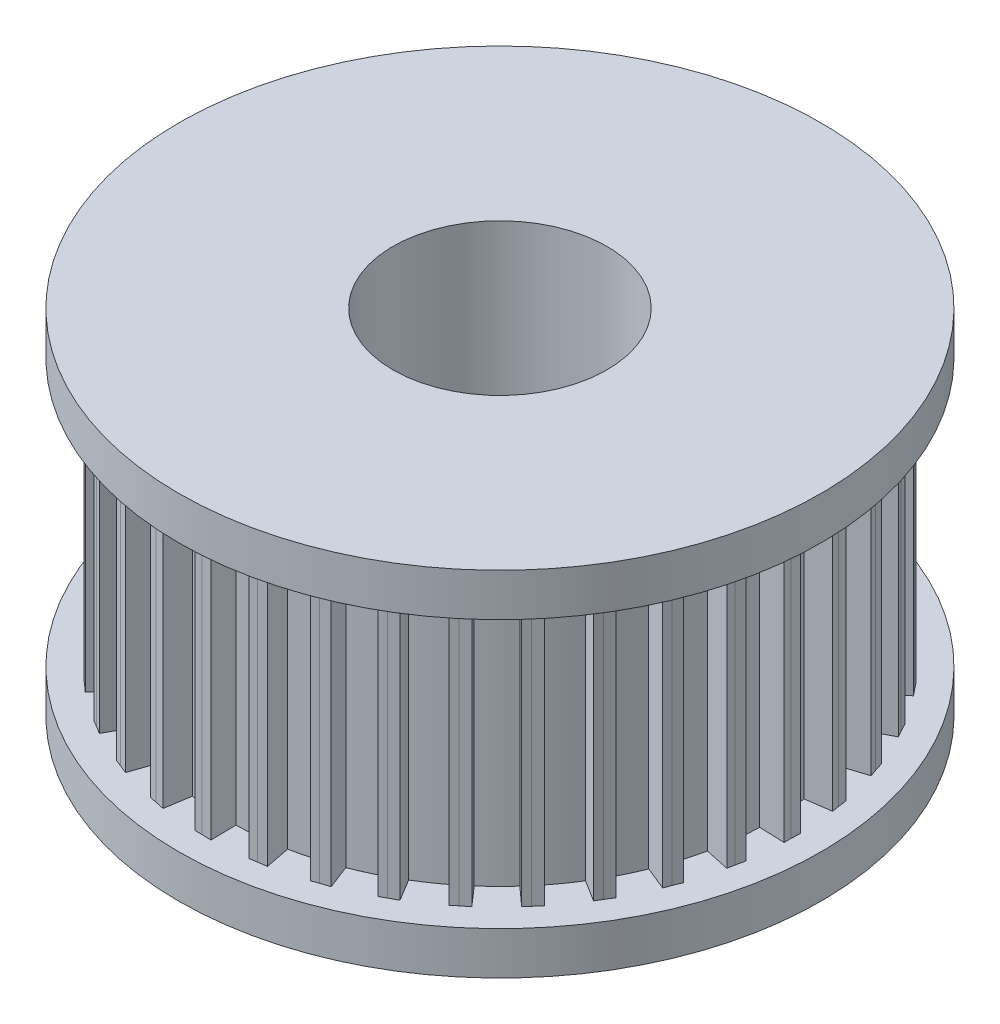
SolidWorks part; units mm, degrees
ref_plane "Front Plane" through (0, 0, 0) normal (0, 0, 1) x (1, 0, 0)
ref_plane "Top Plane" through (0, 0, 0) normal (0, 1, 0) x (1, 0, 0)
ref_plane "Right Plane" through (0, 0, 0) normal (1, 0, 0) x (0, 0, -1)
sketch "Sketch1" plane through (0, 0, 0) normal (0, 1, 0) x (1, 0, 0)
  circle A0 centre (0, 0) radius 6.35
  circle A1 centre (0, 0) radius 19.05
  dimension "D1" = 12.7
  dimension "D2" = 38.1
extrude "Boss-Extrude1" add sketch "Sketch1" along normal blind 2.54
sketch "Sketch2" plane through (0, 2.54, 0) normal (0, 1, 0) x (1, 0, 0)
  line L0 (-6.3084, 16.3202) -> (-5.7627, 14.9085)
  line L1 (-8.5703, 15.2299) -> (-8.2044, 15.4358)
  line L2 (-8.2044, 15.4358) -> (-7.5017, 14.1137)
  line L3 (-7.5017, 14.1137) -> (-8.2044, 15.4358)
  line L4 (-8.5703, 15.2299) -> (-9.0465, 14.9768)
  line L5 (-9.0465, 14.9768) -> (-8.264, 13.6813)
  line L6 (-5.7955, 16.4867) -> (-6.3084, 16.3202)
  line L7 (-5.7955, 16.4867) -> (-5.3994, 16.626)
  line L8 (-5.3994, 16.626) -> (-4.9369, 15.2019)
  line L9 (-3.3786, 17.1677) -> (-3.0864, 15.6827)
  line L10 (-2.8446, 17.2426) -> (-3.3786, 17.1677)
  line L11 (-2.8446, 17.2426) -> (-2.4303, 17.311)
  line L12 (-2.4303, 17.311) -> (-2.2221, 15.8283)
  line L13 (-0.3461, 17.4935) -> (-0.3162, 15.9804)
  line L14 (0.1928, 17.4746) -> (-0.3461, 17.4935)
  line L15 (0.1928, 17.4746) -> (0.6126, 17.47)
  line L16 (0.6126, 17.47) -> (0.5602, 15.9737)
  line L17 (2.6968, 17.2879) -> (2.4636, 15.7925)
  line L18 (3.2243, 17.1757) -> (2.6968, 17.2879)
  line L19 (3.2243, 17.1757) -> (3.637, 17.0982)
  line L20 (3.637, 17.0982) -> (3.3255, 15.6337)
  line L21 (5.6579, 16.5569) -> (5.1685, 15.1248)
  line L22 (6.1579, 16.3548) -> (5.6579, 16.5569)
  line L23 (6.1579, 16.3548) -> (6.5508, 16.2069)
  line L24 (6.5508, 16.2069) -> (5.9897, 14.8188)
  line L25 (8.447, 15.3229) -> (7.7163, 13.9975)
  line L26 (8.9043, 15.0371) -> (8.447, 15.3229)
  line L27 (8.9043, 15.0371) -> (9.2656, 14.8231)
  line L28 (9.2656, 14.8231) -> (8.472, 13.5535)
  line L29 (10.9795, 13.6233) -> (10.0298, 12.4449)
  line L30 (11.3802, 13.2624) -> (10.9795, 13.6233)
  line L31 (11.3802, 13.2624) -> (11.6988, 12.989)
  line L32 (11.6988, 12.989) -> (10.6968, 11.8765)
  line L33 (13.1783, 11.5098) -> (12.0384, 10.5142)
  line L34 (13.5103, 11.0848) -> (13.1783, 11.5098)
  line L35 (13.5103, 11.0848) -> (13.7766, 10.7602)
  line L36 (13.7766, 10.7602) -> (12.5966, 9.8386)
  line L37 (14.9768, 9.0465) -> (13.6813, 8.264)
  line L38 (15.2299, 8.5703) -> (14.9768, 9.0465)
  line L39 (15.2299, 8.5703) -> (15.4358, 8.2044)
  line L40 (15.4358, 8.2044) -> (14.1137, 7.5017)
  line L41 (16.3202, 6.3084) -> (14.9085, 5.7627)
  line L42 (16.4867, 5.7955) -> (16.3202, 6.3084)
  line L43 (16.4867, 5.7955) -> (16.626, 5.3994)
  line L44 (16.626, 5.3994) -> (15.2019, 4.9369)
  line L45 (17.1677, 3.3786) -> (15.6827, 3.0864)
  line L46 (17.2426, 2.8446) -> (17.1677, 3.3786)
  line L47 (17.2426, 2.8446) -> (17.311, 2.4303)
  line L48 (17.311, 2.4303) -> (15.8283, 2.2221)
  line L49 (17.4935, 0.3461) -> (15.9804, 0.3162)
  line L50 (17.4746, -0.1928) -> (17.4935, 0.3461)
  line L51 (17.4746, -0.1928) -> (17.47, -0.6126)
  line L52 (17.47, -0.6126) -> (15.9737, -0.5602)
  line L53 (17.2879, -2.6968) -> (15.7925, -2.4636)
  line L54 (17.1757, -3.2243) -> (17.2879, -2.6968)
  line L55 (17.1757, -3.2243) -> (17.0982, -3.637)
  line L56 (17.0982, -3.637) -> (15.6337, -3.3255)
  line L57 (16.5569, -5.6579) -> (15.1248, -5.1685)
  line L58 (16.3548, -6.1579) -> (16.5569, -5.6579)
  line L59 (16.3548, -6.1579) -> (16.2069, -6.5508)
  line L60 (16.2069, -6.5508) -> (14.8188, -5.9897)
  line L61 (15.3229, -8.447) -> (13.9975, -7.7163)
  line L62 (15.0371, -8.9043) -> (15.3229, -8.447)
  line L63 (15.0371, -8.9043) -> (14.8231, -9.2656)
  line L64 (14.8231, -9.2656) -> (13.5535, -8.472)
  line L65 (13.6233, -10.9795) -> (12.4449, -10.0298)
  line L66 (13.2624, -11.3802) -> (13.6233, -10.9795)
  line L67 (13.2624, -11.3802) -> (12.989, -11.6988)
  line L68 (12.989, -11.6988) -> (11.8765, -10.6968)
  line L69 (11.5098, -13.1783) -> (10.5142, -12.0384)
  line L70 (11.0848, -13.5103) -> (11.5098, -13.1783)
  line L71 (11.0848, -13.5103) -> (10.7602, -13.7766)
  line L72 (10.7602, -13.7766) -> (9.8386, -12.5966)
  line L73 (9.0465, -14.9768) -> (8.264, -13.6813)
  line L74 (8.5703, -15.2299) -> (9.0465, -14.9768)
  line L75 (8.5703, -15.2299) -> (8.2044, -15.4358)
  line L76 (8.2044, -15.4358) -> (7.5017, -14.1137)
  line L77 (6.3084, -16.3202) -> (5.7627, -14.9085)
  line L78 (5.7955, -16.4867) -> (6.3084, -16.3202)
  line L79 (5.7955, -16.4867) -> (5.3994, -16.626)
  line L80 (5.3994, -16.626) -> (4.9369, -15.2019)
  line L81 (3.3786, -17.1677) -> (3.0864, -15.6827)
  line L82 (2.8446, -17.2426) -> (3.3786, -17.1677)
  line L83 (2.8446, -17.2426) -> (2.4303, -17.311)
  line L84 (2.4303, -17.311) -> (2.2221, -15.8283)
  line L85 (0.3461, -17.4935) -> (0.3162, -15.9804)
  line L86 (-0.1928, -17.4746) -> (0.3461, -17.4935)
  line L87 (-0.1928, -17.4746) -> (-0.6126, -17.47)
  line L88 (-0.6126, -17.47) -> (-0.5602, -15.9737)
  line L89 (-2.6968, -17.2879) -> (-2.4636, -15.7925)
  line L90 (-3.2243, -17.1757) -> (-2.6968, -17.2879)
  line L91 (-3.2243, -17.1757) -> (-3.637, -17.0982)
  line L92 (-3.637, -17.0982) -> (-3.3255, -15.6337)
  line L93 (-5.6579, -16.5569) -> (-5.1685, -15.1248)
  line L94 (-6.1579, -16.3548) -> (-5.6579, -16.5569)
  line L95 (-6.1579, -16.3548) -> (-6.5508, -16.2069)
  line L96 (-6.5508, -16.2069) -> (-5.9897, -14.8188)
  line L97 (-8.447, -15.3229) -> (-7.7163, -13.9975)
  line L98 (-8.9043, -15.0371) -> (-8.447, -15.3229)
  line L99 (-8.9043, -15.0371) -> (-9.2656, -14.8231)
  line L100 (-9.2656, -14.8231) -> (-8.472, -13.5535)
  line L101 (-10.9795, -13.6233) -> (-10.0298, -12.4449)
  line L102 (-11.3802, -13.2624) -> (-10.9795, -13.6233)
  line L103 (-11.3802, -13.2624) -> (-11.6988, -12.989)
  line L104 (-11.6988, -12.989) -> (-10.6968, -11.8765)
  line L105 (-13.1783, -11.5098) -> (-12.0384, -10.5142)
  line L106 (-13.5103, -11.0848) -> (-13.1783, -11.5098)
  line L107 (-13.5103, -11.0848) -> (-13.7766, -10.7602)
  line L108 (-13.7766, -10.7602) -> (-12.5966, -9.8386)
  line L109 (-14.9768, -9.0465) -> (-13.6813, -8.264)
  line L110 (-15.2299, -8.5703) -> (-14.9768, -9.0465)
  line L111 (-15.2299, -8.5703) -> (-15.4358, -8.2044)
  line L112 (-15.4358, -8.2044) -> (-14.1137, -7.5017)
  line L113 (-16.3202, -6.3084) -> (-14.9085, -5.7627)
  line L114 (-16.4867, -5.7955) -> (-16.3202, -6.3084)
  line L115 (-16.4867, -5.7955) -> (-16.626, -5.3994)
  line L116 (-16.626, -5.3994) -> (-15.2019, -4.9369)
  line L117 (-17.1677, -3.3786) -> (-15.6827, -3.0864)
  line L118 (-17.2426, -2.8446) -> (-17.1677, -3.3786)
  line L119 (-17.2426, -2.8446) -> (-17.311, -2.4303)
  line L120 (-17.311, -2.4303) -> (-15.8283, -2.2221)
  line L121 (-17.4935, -0.3461) -> (-15.9804, -0.3162)
  line L122 (-17.4746, 0.1928) -> (-17.4935, -0.3461)
  line L123 (-17.4746, 0.1928) -> (-17.47, 0.6126)
  line L124 (-17.47, 0.6126) -> (-15.9737, 0.5602)
  line L125 (-17.2879, 2.6968) -> (-15.7925, 2.4636)
  line L126 (-17.1757, 3.2243) -> (-17.2879, 2.6968)
  line L127 (-17.1757, 3.2243) -> (-17.0982, 3.637)
  line L128 (-17.0982, 3.637) -> (-15.6337, 3.3255)
  line L129 (-16.5569, 5.6579) -> (-15.1248, 5.1685)
  line L130 (-16.3548, 6.1579) -> (-16.5569, 5.6579)
  line L131 (-16.3548, 6.1579) -> (-16.2069, 6.5508)
  line L132 (-16.2069, 6.5508) -> (-14.8188, 5.9897)
  line L133 (-15.3229, 8.447) -> (-13.9975, 7.7163)
  line L134 (-15.0371, 8.9043) -> (-15.3229, 8.447)
  line L135 (-15.0371, 8.9043) -> (-14.8231, 9.2656)
  line L136 (-14.8231, 9.2656) -> (-13.5535, 8.472)
  line L137 (-13.6233, 10.9795) -> (-12.4449, 10.0298)
  line L138 (-13.2624, 11.3802) -> (-13.6233, 10.9795)
  line L139 (-13.2624, 11.3802) -> (-12.989, 11.6988)
  line L140 (-12.989, 11.6988) -> (-11.8765, 10.6968)
  line L141 (-11.5098, 13.1783) -> (-10.5142, 12.0384)
  line L142 (-11.0848, 13.5103) -> (-11.5098, 13.1783)
  line L143 (-11.0848, 13.5103) -> (-10.7602, 13.7766)
  line L144 (-10.7602, 13.7766) -> (-9.8386, 12.5966)
  circle A0 centre (0, 0) radius 6.35
  circle A1 centre (0, 0) radius 15.9835
  point P186 (0, 0)
  dimension "D1" = 36
extrude "Boss-Extrude2" add sketch "Sketch2" along normal blind 15.875 contours A1 region at (-5.2005, 2.54, -14.6349)
extrude "Boss-Extrude3" add sketch "Sketch2<6>" along normal blind 15.875 contours A1 L72 L71 L70 L69 | A1 L68 L67 L66 L65 | A1 L64 L63 L62 L61 | A1 L60 L59 L58 L57 | A1 L56 L55 L54 L53 | A1 L52 L51 L50 L49 | A1 L48 L47 L46 L45 | A1 L44 L43 L42 L41 | A1 L40 L39 L38 L37 | A1 L36 L35 L34 L33 | A1 L32 L31 L30 L29 | A1 L28 L27 L26 L25 | A1 L24 L23 L22 L21 | A1 L20 L19 L18 L17 | A1 L16 L15 L14 L13 | A1 L12 L11 L10 L9 | A1 L8 L7 L6 L0 | A1 L2 L1 L4 L5 | A1 L144 L143 L142 L141 | A1 L140 L139 L138 L137 | A1 L136 L135 L134 L133 | A1 L132 L131 L130 L129 | A1 L128 L127 L126 L125 | A1 L124 L123 L122 L121 | A1 L120 L119 L118 L117 | A1 L116 L115 L114 L113 | A1 L112 L111 L110 L109 | A1 L108 L107 L106 L105 | A1 L104 L103 L102 L101 | A1 L100 L99 L98 L97 | A1 L96 L95 L94 L93 | A1 L92 L91 L90 L89 | A1 L88 L87 L86 L85 | A1 L84 L83 L82 L81 | A1 L80 L79 L78 L77 | A1 L76 L75 L74 L73 region at (-5.6066, 2.54, -15.7749) region at (-8.2607, 2.54, -14.5617) region at (-2.7821, 2.54, -16.5089) region at (-10.6638, 2.54, -12.906) region at (0.1269, 2.54, -16.7412) region at (-12.7429, 2.54, -10.8582) region at (3.032, 2.54, -16.4648) region at (-14.4348, 2.54, -8.4805) region at (5.845, 2.54, -15.6882) region at (-15.6882, 2.54, -5.845) region at (8.4805, 2.54, -14.4348) region at (-16.4648, 2.54, -3.032) region at (10.8582, 2.54, -12.7429) region at (-16.7412, 2.54, -0.1269) region at (12.906, 2.54, -10.6638) region at (-16.5089, 2.54, 2.7821) region at (14.5617, 2.54, -8.2607) region at (-15.7749, 2.54, 5.6066) region at (15.7749, 2.54, -5.6066) region at (-14.5617, 2.54, 8.2607) region at (16.5089, 2.54, -2.7821) region at (-12.906, 2.54, 10.6638) region at (16.7412, 2.54, 0.1269) region at (-10.8582, 2.54, 12.7429) region at (16.4648, 2.54, 3.032) region at (-8.4805, 2.54, 14.4348) region at (15.6882, 2.54, 5.845) region at (-5.845, 2.54, 15.6882) region at (14.4348, 2.54, 8.4805) region at (-3.032, 2.54, 16.4648) region at (12.7429, 2.54, 10.8582) region at (-0.1269, 2.54, 16.7412) region at (10.6638, 2.54, 12.906) region at (2.7821, 2.54, 16.5089) region at (8.2607, 2.54, 14.5617) region at (5.6066, 2.54, 15.7749)
sketch "Sketch2<6>" plane through (0, 2.54, 0) normal (0, 1, 0) x (1, 0, 0) same geometry as "Sketch2"
sketch "Sketch4" plane through (0, 18.415, 0) normal (0, 1, 0) x (1, 0, 0)
  circle A0 centre (0, 0) radius 6.35
  circle A1 centre (0, 0) radius 19.05
  dimension "D1" = 38.1
extrude "Boss-Extrude4" add sketch "Sketch4" along normal blind 2.54
